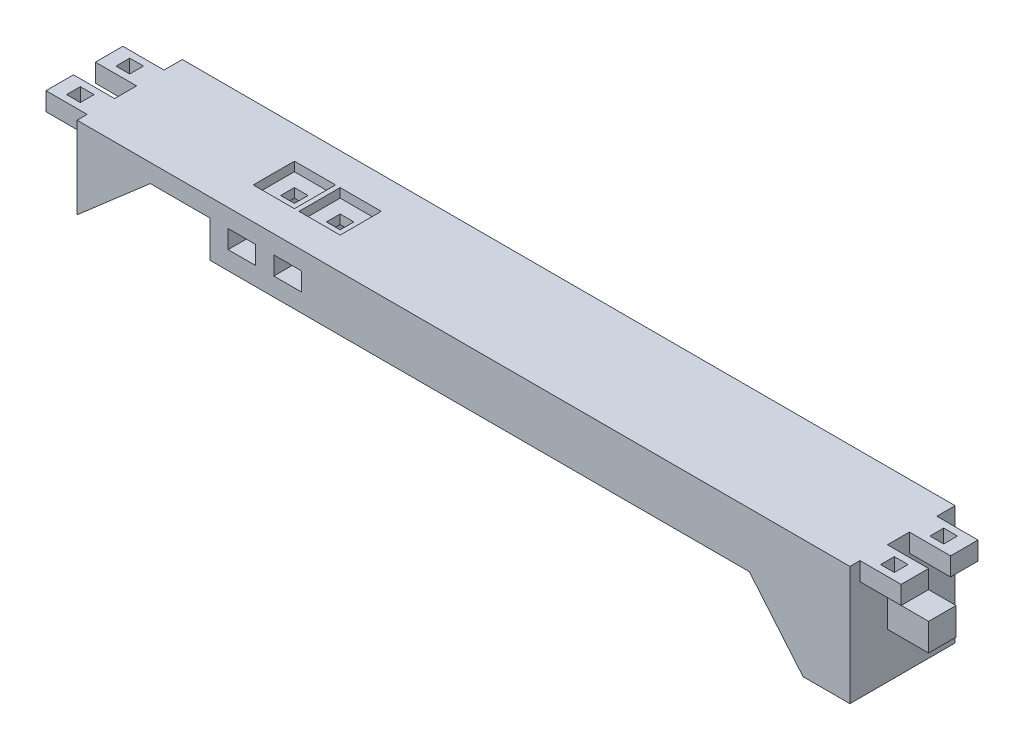
SolidWorks part; units mm, degrees
ref_plane "Front Plane" through (0, 0, 0) normal (0, 0, 1) x (1, 0, 0)
ref_plane "Top Plane" through (0, 0, 0) normal (0, 1, 0) x (1, 0, 0)
ref_plane "Right Plane" through (0, 0, 0) normal (1, 0, 0) x (0, 0, -1)
sketch "Sketch1" plane through (0, 0, 0) normal (0, 1, 0) x (1, 0, 0)
  line L1 (0, 0) -> (186.97, 0)
  line L2 (0, 0) -> (0, 23)
  line L3 (0, 23) -> (186.97, 23)
  line L4 (186.97, 0) -> (186.97, 23)
  dimension "D1" = 23
  dimension "D2" = 186.97
extrude "Boss-Extrude1" add sketch "Sketch1" along normal blind 4
sketch "Sketch2" plane through (0, 0, 0) normal (0, -1, 0) x (1, 0, 0)
  line L0 (186.97, -23) -> (0, -23) construction
  line L1 (177.97, 0) -> (167.97, 0)
  line L2 (177.97, 0) -> (177.97, -23)
  line L3 (177.97, -23) -> (167.97, -23)
  line L4 (167.97, 0) -> (167.97, -23)
  dimension "D1" = 10
extrude "Boss-Extrude2" add sketch "Sketch2" along normal blind 22
sketch "Sketch3" plane through (0, 0, 0) normal (0, -1, 0) x (1, 0, 0)
  line L0 (167.97, 0) -> (167.97, -23) construction
  line L1 (167.97, 0) -> (38.01, 0)
  line L2 (167.97, 0) -> (167.97, -8)
  line L3 (167.97, -8) -> (62.01, -8)
  line L4 (38.01, 0) -> (38.01, -8)
  line L5 (167.97, -23) -> (0, -23) construction
  line L7 (38.01, -8) -> (38.01, -23)
  line L8 (38.01, -23) -> (62.01, -23)
  line L9 (62.01, -8) -> (62.01, -23)
  dimension "D1" = 129.96
  dimension "D2" = 8
  dimension "D3" = 24
extrude "Boss-Extrude3" add sketch "Sketch3" along normal blind 8
chamfer "Chamfer1" distance 12 angle 50 1 edges at (167.97, -8, -4) first distance on face at (89.33, -8, -10.3333)
sketch "Sketch4" plane through (0, 0, 0) normal (0, -1, 0) x (1, 0, 0)
  line L6 (186.97, 0) -> (186.97, -23) construction
  line L11 (186.97, -8.2) -> (177.97, -8.2)
  line L12 (186.97, -8.2) -> (186.97, -13)
  line L13 (186.97, -13) -> (177.97, -13)
  line L14 (177.97, -8.2) -> (177.97, -13)
  line L15 (177.97, -23) -> (177.97, 0) construction
  line L17 (186.97, -23) -> (177.97, -23) construction
  line L18 (0, -23) -> (0, 0) construction
  line L19 (186.97, -23) -> (177.97, -23)
  line L20 (186.97, -23) -> (186.97, -19)
  line L21 (186.97, -19) -> (177.97, -19)
  line L22 (177.97, -23) -> (177.97, -19)
  line L23 (186.97, 0) -> (177.97, 0)
  line L24 (186.97, 0) -> (186.97, -2.2)
  line L25 (186.97, -2.2) -> (177.97, -2.2)
  line L26 (177.97, 0) -> (177.97, -2.2)
  line L27 (180.97, -14.5) -> (183.97, -14.5)
  line L28 (180.97, -14.5) -> (180.97, -17.5)
  line L29 (180.97, -17.5) -> (183.97, -17.5)
  line L30 (183.97, -14.5) -> (183.97, -17.5)
  line L31 (180.97, -3.7) -> (183.97, -3.7)
  line L32 (180.97, -3.7) -> (180.97, -6.7)
  line L33 (180.97, -6.7) -> (183.97, -6.7)
  line L34 (183.97, -3.7) -> (183.97, -6.7)
  line L35 (0, 0) -> (9, 0)
  line L36 (0, 0) -> (0, -2.2)
  line L37 (0, -2.2) -> (9, -2.2)
  line L38 (9, 0) -> (9, -2.2)
  line L39 (3, -3.7) -> (6, -3.7)
  line L40 (3, -3.7) -> (3, -6.7)
  line L41 (3, -6.7) -> (6, -6.7)
  line L42 (6, -3.7) -> (6, -6.7)
  line L44 (0, -8.2) -> (9, -8.2)
  line L45 (0, -8.2) -> (0, -13)
  line L46 (0, -13) -> (9, -13)
  line L47 (9, -8.2) -> (9, -13)
  line L48 (3, -14.5) -> (6, -14.5)
  line L49 (3, -14.5) -> (3, -17.5)
  line L50 (3, -17.5) -> (6, -17.5)
  line L51 (6, -14.5) -> (6, -17.5)
  line L52 (0, -23) -> (9, -23)
  line L53 (0, -23) -> (0, -19)
  line L54 (0, -19) -> (9, -19)
  line L55 (9, -23) -> (9, -19)
  dimension "D1" = 4.8
  dimension "D2" = 10
  dimension "D3" = 6
  dimension "D4" = 6
  dimension "D5" = 3
  dimension "D6" = 3
  dimension "D7" = 3
  dimension "D8" = 1.5
  dimension "D9" = 3
  dimension "D10" = 3
  dimension "D11" = 3
  dimension "D12" = 1.5
  dimension "D13" = 9
  dimension "D14" = 3
  dimension "D15" = 3
  dimension "D16" = 3
  dimension "D17" = 1.5
  dimension "D18" = 1.5
  dimension "D19" = 4.8
  dimension "D20" = 3
  dimension "D21" = 3
  dimension "D22" = 1.5
  dimension "D23" = 3
  dimension "D24" = 1.5
extrude "Cut-Extrude1" cut sketch "Sketch4" against normal up to next
sketch "Sketch5" plane through (177.97, 0, 0) normal (1, 0, 0) x (0, 0, -1)
  line L0 (8.2, 0) -> (2.2, 0) construction
  line L1 (8.2, -6) -> (14.2, -6)
  line L2 (8.2, -6) -> (8.2, -12)
  line L3 (8.2, -12) -> (14.2, -12)
  line L4 (14.2, -6) -> (14.2, -12)
  line L5 (2.2, 4) -> (2.2, 0) construction
  dimension "D1" = 6
  dimension "D2" = 6
  dimension "D3" = 6
  dimension "D4" = 6
extrude "Boss-Extrude4" add sketch "Sketch5" along normal blind 9
sketch "Sketch6" plane through (0, 0, -23) normal (0, 0, -1) x (-1, 0, 0)
  line L0 (-177.97, 4) -> (-9, 4) construction
  line L1 (-58.01, 0) -> (-52.01, 0)
  line L2 (-58.01, 0) -> (-58.01, -4)
  line L3 (-58.01, -4) -> (-52.01, -4)
  line L4 (-52.01, 0) -> (-52.01, -4)
  line L5 (-62.01, -8) -> (-62.01, 0) construction
  line L7 (-48.01, 0) -> (-42.01, 0)
  line L8 (-48.01, 0) -> (-48.01, -4)
  line L9 (-48.01, -4) -> (-42.01, -4)
  line L10 (-42.01, 0) -> (-42.01, -4)
  dimension "D1" = 6
  dimension "D2" = 4
  dimension "D3" = 4
  dimension "D4" = 4
  dimension "D5" = 6
  dimension "D6" = 4
extrude "Cut-Extrude2" cut sketch "Sketch6" against normal up to next
sketch "Sketch7" plane through (0, 4, 0) normal (0, 1, 0) x (1, 0, 0)
  line L0 (177.97, 23) -> (9, 23) construction
  line L1 (43.51, 13) -> (46.51, 13)
  line L2 (43.51, 13) -> (43.51, 10)
  line L3 (43.51, 10) -> (46.51, 10)
  line L4 (46.51, 13) -> (46.51, 10)
  line L5 (38.01, 0) -> (38.01, 23) construction
  line L7 (53.51, 13) -> (56.51, 13)
  line L8 (53.51, 13) -> (53.51, 10)
  line L9 (53.51, 10) -> (56.51, 10)
  line L10 (56.51, 13) -> (56.51, 10)
  dimension "D1" = 10
  dimension "D2" = 3
  dimension "D3" = 5.5
  dimension "D4" = 3
  dimension "D5" = 3
  dimension "D6" = 7
extrude "Cut-Extrude3" cut sketch "Sketch7" against normal up to next
sketch "Sketch8" plane through (0, 0, 0) normal (0, -1, 0) x (1, 0, 0)
  line L0 (38.01, -23) -> (9, -23) construction
  line L1 (9, 0) -> (25, 0)
  line L2 (9, 0) -> (9, -23)
  line L3 (9, -23) -> (25, -23)
  line L4 (25, 0) -> (25, -23)
  dimension "D1" = 16
extrude "Boss-Extrude5" add sketch "Sketch8" along normal blind 14
chamfer "Chamfer2" distance 14 angle 49 1 edges at (25, -14, -11.5) first distance on face at (25, -7, -11.5)
sketch "Sketch9" plane through (0, 4, 0) normal (0, 1, 0) x (1, 0, 0)
  line L0 (46.51, 13) -> (43.51, 13) construction
  line L1 (49.51, 16) -> (40.51, 16)
  line L2 (49.51, 16) -> (49.51, 7)
  line L3 (49.51, 7) -> (40.51, 7)
  line L4 (40.51, 16) -> (40.51, 7)
  line L5 (43.51, 13) -> (43.51, 10) construction
  line L6 (46.51, 10) -> (46.51, 13) construction
  line L7 (43.51, 10) -> (46.51, 10) construction
  line L8 (56.51, 13) -> (53.51, 13) construction
  line L9 (50.51, 16) -> (59.51, 16)
  line L10 (50.51, 16) -> (50.51, 7)
  line L11 (50.51, 7) -> (59.51, 7)
  line L12 (59.51, 16) -> (59.51, 7)
  line L13 (53.51, 13) -> (53.51, 10) construction
  line L14 (56.51, 10) -> (56.51, 13) construction
  line L15 (53.51, 10) -> (56.51, 10) construction
  dimension "D1" = 3
  dimension "D2" = 3
  dimension "D3" = 3
  dimension "D4" = 3
  dimension "D5" = 3
  dimension "D6" = 3
  dimension "D7" = 3
  dimension "D8" = 3
extrude "Cut-Extrude4" cut sketch "Sketch9" against normal blind 2
